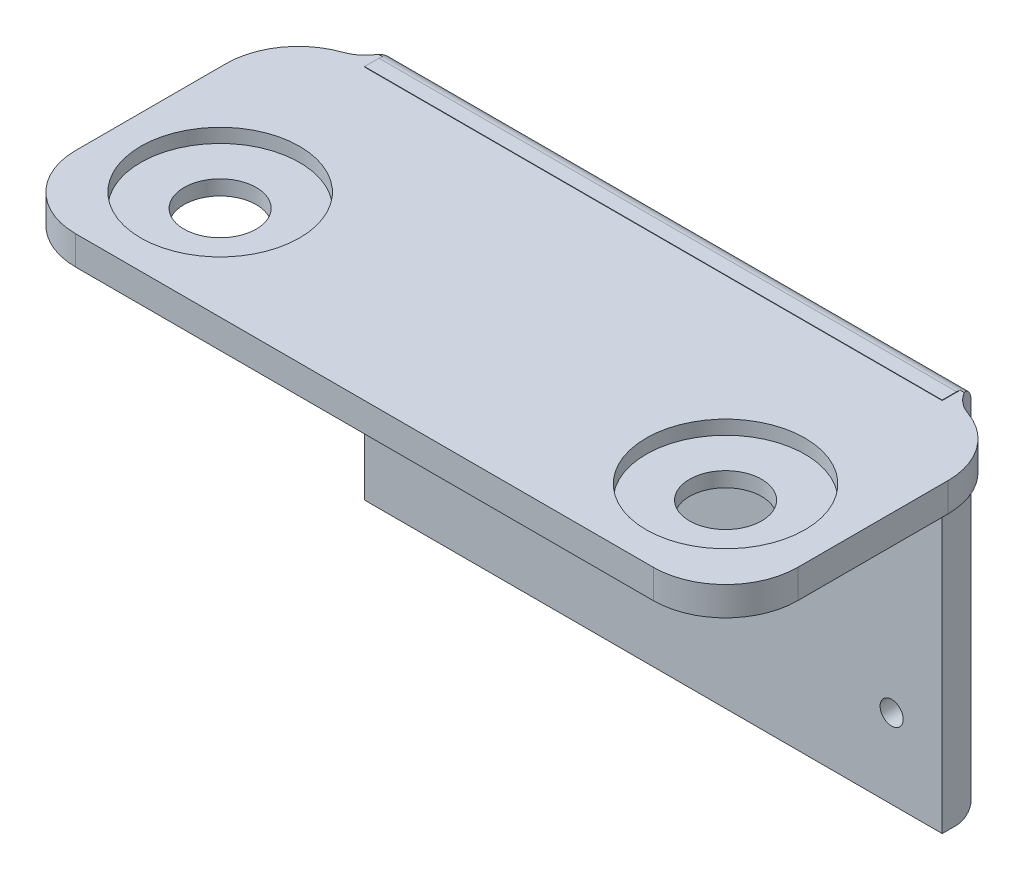
SolidWorks part; units mm, degrees
material "Du"
ref_plane "Front Plane" through (0, 0, 0) normal (0, 0, 1) x (1, 0, 0)
ref_plane "Top Plane" through (0, 0, 0) normal (0, 1, 0) x (1, 0, 0)
ref_plane "Right Plane" through (0, 0, 0) normal (1, 0, 0) x (0, 0, -1)
sketch "Sketch1" plane through (0, 0, 0) normal (0, 0, 1) x (1, 0, 0)
  line L1 (-40, 26) -> (40, 26)
  line L2 (-40, 26) -> (-40, -26)
  line L3 (-40, -26) -> (40, -26)
  line L4 (40, 26) -> (40, -26)
  line L5 (-40, 26) -> (40, -26) construction
  line L6 (-40, -26) -> (40, 26) construction
  point P1 (0, 0)
  dimension "D1" = 80
  dimension "D2" = 52
extrude "Boss-Extrude1" add sketch "Sketch1" along normal blind 4
sketch "Sketch2" plane through (0, 0.9399, 4) normal (0, 0, 1) x (1, 0, 0)
  line L1 (-50, 25) -> (50, 25)
  line L2 (-50, 25) -> (-50, 21)
  line L3 (-50, 21) -> (50, 21)
  line L4 (50, 25) -> (50, 21)
  line L5 (-50, 25) -> (50, 21) construction
  line L6 (-50, 21) -> (50, 25) construction
  point P0 (0, 23)
  dimension "D1" = 100
  dimension "D2" = 4
extrude "Boss-Extrude2" add sketch "Sketch2" along normal blind 40
fillet "Fillet1" radius 5 1 edges at (0, 21.9399, 4)
fillet "Fillet2" radius 5 2 edges at (-40, 23.9399, 4) (40, 23.9399, 4)
fillet "Fillet4" radius 5 2 edges at (-40, 21.9399, 4.5) (40, 21.9399, 4.5)
sketch "Sketch6" plane through (0, 26, 0) normal (0, 1, 0) x (1, 0, 0)
  line L0 (-50, -44) -> (-50, -4) construction
  line L1 (50, -44) -> (-50, -44) construction
  line L2 (50, -44) -> (50, -4) construction
  circle A0 centre (-35, -29) radius 11
  circle A1 centre (35, -29) radius 11
  dimension "D1" = 22
  dimension "D2" = 22
  dimension "D3" = 15
  dimension "D4" = 15
  dimension "D5" = 15
  dimension "D6" = 15
extrude "Cut-Extrude3" cut sketch "Sketch6" against normal blind 2
sketch "Sketch7" plane through (0, 24, 0) normal (0, 1, 0) x (1, 0, 0)
  circle A0 centre (-35, -29) radius 5
  circle A1 centre (35, -29) radius 5
  dimension "D1" = 10
  dimension "D2" = 10
extrude "Cut-Extrude4" cut sketch "Sketch7" against normal through all
sketch "Sketch9" plane through (0, 0, 0) normal (0, 0, -1) x (-1, 0, 0)
  circle A0 centre (0, 0) radius 11
  dimension "D1" = 22
extrude "Cut-Extrude5" cut sketch "Sketch9" against normal blind 2
sketch "Sketch10" plane through (0, 0, 2) normal (0, 0, -1) x (-1, 0, 0)
  circle A0 centre (0, 0) radius 5
  dimension "D1" = 10
extrude "Cut-Extrude6" cut sketch "Sketch10" against normal blind 2
fillet "Fillet6" radius 10 2 edges at (50, 23.9399, 44) (-50, 23.9399, 44)
fillet "Fillet7" radius 10 2 edges at (50, 23.9399, 4) (-50, 23.9399, 4)
fillet "Fillet8" radius 2 2 edges at (0, -26, 0) (0, 26, 0)
sketch "Sketch12" plane through (0, 0, 4) normal (0, 0, 1) x (1, 0, 0)
  line L0 (-40, -26) -> (40, -26) construction
  line L1 (-40, 16.9399) -> (-40, -26) construction
  line L2 (40, -26) -> (40, 16.9399) construction
  circle A0 centre (-33, -15) radius 1.6
  circle A3 centre (33, -15) radius 1.6
  dimension "D1" = 3.2
  dimension "D2" = 11
  dimension "D5" = 11
  dimension "D6" = 7
  dimension "D7" = 7
extrude "Cut-Extrude7" cut sketch "Sketch12" against normal through all
